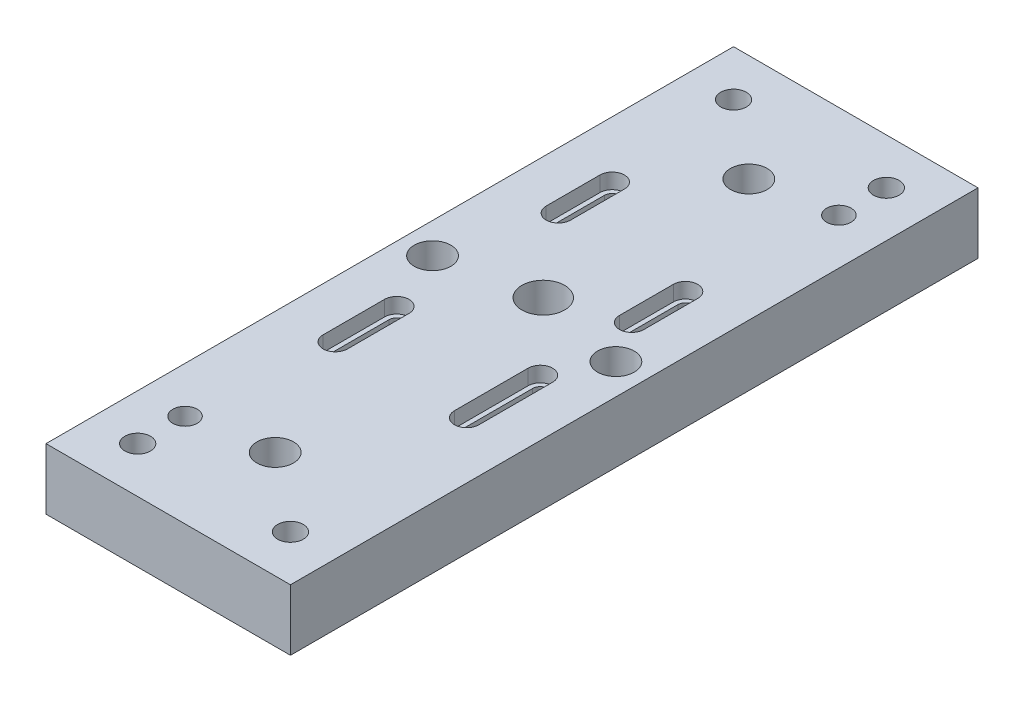
SolidWorks part; units mm, degrees
material "Plain Carbon Steel"
ref_plane "Front Plane" through (0, 0, 0) normal (0, 0, 1) x (1, 0, 0)
ref_plane "Top Plane" through (0, 0, 0) normal (0, 1, 0) x (1, 0, 0)
ref_plane "Right Plane" through (0, 0, 0) normal (1, 0, 0) x (0, 0, -1)
sketch "Sketch1" plane through (0, 0, 0) normal (0, 1, 0) x (1, 0, 0)
  line L1 (-40, -112.5) -> (40, -112.5)
  line L2 (-40, -112.5) -> (-40, 112.5)
  line L3 (-40, 112.5) -> (40, 112.5)
  line L4 (40, -112.5) -> (40, 112.5)
  line L5 (-40, -112.5) -> (40, 112.5) construction
  line L6 (-40, 112.5) -> (40, -112.5) construction
  point P0 (0, 0)
  dimension "D1" = 225
  dimension "D2" = 80
extrude "Boss-Extrude1" add sketch "Sketch1" against normal blind 20
sketch "Sketch2" plane through (0, 0, 0) normal (0, 1, 0) x (1, 0, 0)
  line L4 (24, 17.68) -> (24, 35.28)
  line L5 (19, 35.28) -> (19, 17.68)
  line L6 (24, 17.68) -> (24, 35.28)
  line L7 (19, 35.28) -> (19, 17.68)
  line L10 (24, -36.32) -> (24, -12.22)
  line L11 (19, -12.22) -> (19, -36.32)
  line L12 (24, -36.32) -> (24, -12.22)
  line L13 (19, -12.22) -> (19, -36.32)
  line L16 (-24, -16.22) -> (-24, -36.32)
  line L17 (-19, -36.32) -> (-19, -16.22)
  line L18 (-24, -16.22) -> (-24, -36.32)
  line L19 (-19, -36.32) -> (-19, -16.22)
  line L22 (-24, 54.28) -> (-24, 36.68)
  line L23 (-19, 36.68) -> (-19, 54.28)
  line L24 (-24, 54.28) -> (-24, 36.68)
  line L25 (-19, 36.68) -> (-19, 54.28)
  arc A4 (24, 35.28) -> (19, 35.28) centre (21.5, 35.28) ccw
  arc A5 (19, 17.68) -> (24, 17.68) centre (21.5, 17.68) ccw
  arc A6 (24, 35.28) -> (19, 35.28) centre (21.5, 35.28) ccw
  arc A7 (19, 17.68) -> (24, 17.68) centre (21.5, 17.68) ccw
  arc A10 (24, -12.22) -> (19, -12.22) centre (21.5, -12.22) ccw
  arc A11 (19, -36.32) -> (24, -36.32) centre (21.5, -36.32) ccw
  arc A12 (24, -12.22) -> (19, -12.22) centre (21.5, -12.22) ccw
  arc A13 (19, -36.32) -> (24, -36.32) centre (21.5, -36.32) ccw
  arc A16 (-24, -36.32) -> (-19, -36.32) centre (-21.5, -36.32) ccw
  arc A17 (-19, -16.22) -> (-24, -16.22) centre (-21.5, -16.22) ccw
  arc A18 (-24, -36.32) -> (-19, -36.32) centre (-21.5, -36.32) ccw
  arc A19 (-19, -16.22) -> (-24, -16.22) centre (-21.5, -16.22) ccw
  arc A22 (-24, 36.68) -> (-19, 36.68) centre (-21.5, 36.68) ccw
  arc A23 (-19, 54.28) -> (-24, 54.28) centre (-21.5, 54.28) ccw
  arc A24 (-24, 36.68) -> (-19, 36.68) centre (-21.5, 36.68) ccw
  arc A25 (-19, 54.28) -> (-24, 54.28) centre (-21.5, 54.28) ccw
  dimension "D2" = 0.05
  dimension "D1" = 0.05
  dimension "D3" = 0.05
  dimension "D4" = 0.05
extrude "Cut-Extrude1" cut sketch "Sketch2" against normal up to next
sketch "Sketch3" plane through (0, 0, 0) normal (0, 1, 0) x (1, 0, 0)
  line L4 (-17.5, 36.68) -> (-17.5, 54.28)
  line L5 (-25.5, 54.28) -> (-25.5, 36.68)
  line L6 (-17.5, 36.68) -> (-17.5, 54.28)
  line L7 (-25.5, 54.28) -> (-25.5, 36.68)
  line L10 (25.5, 17.68) -> (25.5, 35.28)
  line L11 (17.5, 35.28) -> (17.5, 17.68)
  line L12 (25.5, 17.68) -> (25.5, 35.28)
  line L13 (17.5, 35.28) -> (17.5, 17.68)
  line L16 (25.5, -36.32) -> (25.5, -12.22)
  line L17 (17.5, -12.22) -> (17.5, -36.32)
  line L18 (25.5, -36.32) -> (25.5, -12.22)
  line L19 (17.5, -12.22) -> (17.5, -36.32)
  line L22 (-25.5, -16.22) -> (-25.5, -36.32)
  line L23 (-17.5, -36.32) -> (-17.5, -16.22)
  line L24 (-25.5, -16.22) -> (-25.5, -36.32)
  line L25 (-17.5, -36.32) -> (-17.5, -16.22)
  arc A4 (-17.5, 54.28) -> (-25.5, 54.28) centre (-21.5, 54.28) ccw
  arc A5 (-25.5, 36.68) -> (-17.5, 36.68) centre (-21.5, 36.68) ccw
  arc A6 (-17.5, 54.28) -> (-25.5, 54.28) centre (-21.5, 54.28) ccw
  arc A7 (-25.5, 36.68) -> (-17.5, 36.68) centre (-21.5, 36.68) ccw
  arc A10 (25.5, 35.28) -> (17.5, 35.28) centre (21.5, 35.28) ccw
  arc A11 (17.5, 17.68) -> (25.5, 17.68) centre (21.5, 17.68) ccw
  arc A12 (25.5, 35.28) -> (17.5, 35.28) centre (21.5, 35.28) ccw
  arc A13 (17.5, 17.68) -> (25.5, 17.68) centre (21.5, 17.68) ccw
  arc A16 (25.5, -12.22) -> (17.5, -12.22) centre (21.5, -12.22) ccw
  arc A17 (17.5, -36.32) -> (25.5, -36.32) centre (21.5, -36.32) ccw
  arc A18 (25.5, -12.22) -> (17.5, -12.22) centre (21.5, -12.22) ccw
  arc A19 (17.5, -36.32) -> (25.5, -36.32) centre (21.5, -36.32) ccw
  arc A22 (-25.5, -36.32) -> (-17.5, -36.32) centre (-21.5, -36.32) ccw
  arc A23 (-17.5, -16.22) -> (-25.5, -16.22) centre (-21.5, -16.22) ccw
  arc A24 (-25.5, -36.32) -> (-17.5, -36.32) centre (-21.5, -36.32) ccw
  arc A25 (-17.5, -16.22) -> (-25.5, -16.22) centre (-21.5, -16.22) ccw
  dimension "D1" = 1.5
  dimension "D2" = 1.5
  dimension "D3" = 1.5
  dimension "D4" = 1.5
extrude "Cut-Extrude2" cut sketch "Sketch3" against normal blind 5
hole_wizard "CBORE for M8 Hex Socket Head Cap Screw1" positions "Sketch7" profile "Sketch6" counterbore size "M8" standard "ISO" end condition through all
sketch "Sketch7" plane through (0, -20, 0) normal (0, -1, 0) x (-1, 0, 0)
  line L0 (-40, -112.5) -> (-40, 112.5) construction
  line L1 (-40, 112.5) -> (40, 112.5) construction
  line L2 (40, 112.5) -> (40, -112.5) construction
  line L3 (40, -112.5) -> (-40, -112.5) construction
  point P0 (-25, 97.5)
  point P2 (25, 97.5)
  point P4 (25, -97.5)
  point P6 (-25, -97.5)
  point P15 (0, 0)
  point P20 (0, 0)
  point P21 (0, 0)
  point P22 (0, 0)
  point P23 (0, 0)
  dimension "D1" = 15
  dimension "D2" = 15
  dimension "D3" = 15
  dimension "D4" = 15
sketch "Sketch6" plane through (25, -20, -97.5) normal (1, 0, 0) x (0, 0, -1)
  line L0 (0, 0) -> (0, 20)
  line L1 (0, 20) -> (4.2, 20)
  line L3 (4.2, 20) -> (4.2, 8.6)
  line L4 (7.5, 8.6) -> (4.2, 8.6)
  line L5 (7.5, 8.6) -> (7.5, 0.025)
  line L6 (7.5, 0.025) -> (7.525, 0)
  line L7 (7.525, 0) -> (0, 0)
  line L8 (-7.5, 0.025) -> (-7.525, 0) construction
  line L11 (0, -6.35) -> (0, 107.95) construction
  dimension "Thru Hole Dia." = 8.4
  dimension "Thru Hole Depth" = 20
  dimension "C'Bore Dia." = 15
  dimension "C'Bore Depth" = 8.6
  dimension "Near C'Sink Dia." = 15.05
  dimension "Near C'Sink Angle" = 90
hole_wizard "Ø8.0mm Dowel Hole1" positions "Sketch12" profile "Sketch9" hole size "Ø8.0" standard "ISO" end condition through all
sketch "Sketch12" plane through (0, -20, 0) normal (0, -1, 0) x (-1, 0, 0)
  line L4 (25, -97.5) -> (25, -82) construction
  line L6 (-25, 97.5) -> (-25, 81.975) construction
  circle A1 centre (25, -97.5) radius 7.5 construction
  circle A3 centre (-25, 97.5) radius 7.525 construction
  point P0 (-25, 81.975)
  point P2 (25, -82)
  point P40 (0, 0)
  dimension "D1" = 8
  dimension "D2" = 8
sketch "Sketch9" plane through (25, -20, -81.975) normal (1, 0, 0) x (0, 0, -1)
  line L0 (0, 0) -> (0, 20)
  line L1 (0, 20) -> (4, 20)
  line L2 (4, 20) -> (4, 0)
  line L5 (4, 0) -> (0, 0)
  line L11 (0, -6.35) -> (0, 107.95) construction
  dimension "Thru Hole Dia." = 8
  dimension "Thru Hole Depth" = 20
sketch "Sketch11" plane through (0, -20, 0) normal (0, -1, 0) x (1, 0, 0)
  circle A0 centre (-22, 55) radius 10.5
  circle A1 centre (22, 55) radius 10.5
  circle A2 centre (-22, -72) radius 10.5
  circle A3 centre (22, -60) radius 10.5
  circle A4 centre (0, -35) radius 10.5
  circle A5 centre (0, 25) radius 10.5
  point P12 (0, 0)
  point P14 (0, 0)
  point P15 (0, 0)
  point P16 (0, 0)
  point P17 (22, -59.2209)
  point P18 (0, 0)
  dimension "D1" = 21
  dimension "D2" = 35
  dimension "D3" = 25
  dimension "D4" = 72
  dimension "D5" = 22
  dimension "D6" = 22
  dimension "D7" = 55
  dimension "D8" = 60
extrude "Cut-Extrude3" cut sketch "Sketch11" against normal blind 14.2
sketch "Sketch13" plane through (0, 0, 0) normal (0, 1, 0) x (1, 0, 0)
  circle A0 centre (0, 77.5) radius 6
  circle A1 centre (0, -77.5) radius 6
  circle A2 centre (-30, 4) radius 6
  circle A3 centre (30, 4) radius 6
  dimension "D1" = 12
extrude "Cut-Extrude4" cut sketch "Sketch13" against normal up to next
sketch "Sketch14" plane through (0, 0, 0) normal (0, 1, 0) x (1, 0, 0)
  circle A0 centre (0, 10.23) radius 5 construction
  circle A1 centre (0, 10.23) radius 5 construction
  circle A2 centre (0, 10.23) radius 7
  dimension "D1" = 14
extrude "Cut-Extrude5" cut sketch "Sketch14" against normal up to next
